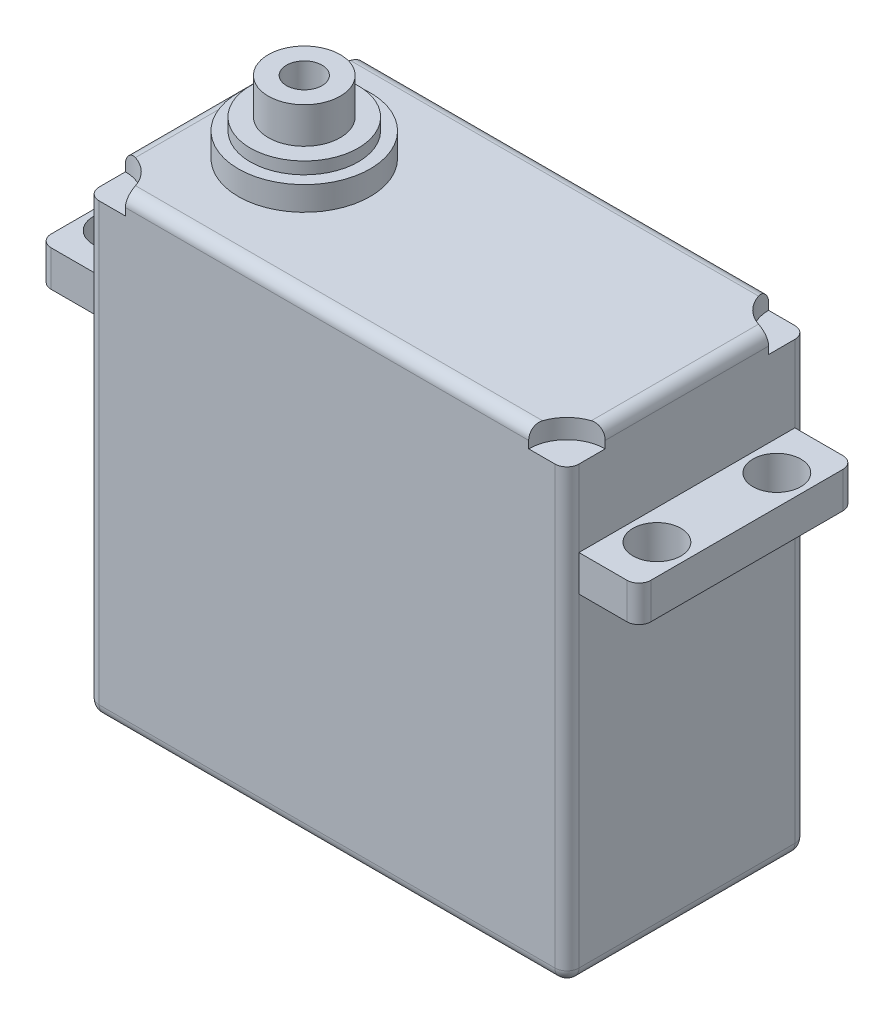
SolidWorks part; units mm, degrees
ref_plane "前视基准面" through (0, 0, 0) normal (0, 0, 1) x (1, 0, 0)
ref_plane "上视基准面" through (0, 0, 0) normal (0, 1, 0) x (1, 0, 0)
ref_plane "右视基准面" through (0, 0, 0) normal (1, 0, 0) x (0, 0, -1)
other "Configuration Table"
sketch "草图1" plane through (0, 0, 0) normal (0, 0, 1) x (1, 0, 0)
  line L0 (-19.2, 17.8947) -> (-19.2, -17.89)
  line L1 (-20, 19.5) -> (20, 19.5)
  line L2 (-20, 19.5) -> (-20, -19.5)
  line L3 (-20, -19.5) -> (20, -19.5)
  line L4 (20, 19.5) -> (20, -19.5)
  line L5 (-20, 19.5) -> (20, -19.5) construction
  line L6 (-20, -19.5) -> (20, 19.5) construction
  line L9 (-20, 17.8947) -> (-16.8102, 17.8947)
  line L10 (-16.8102, 19.5) -> (-16.8102, 17.8947)
  line L13 (-20, -17.89) -> (-16.81, -17.89)
  line L14 (-16.81, -19.5) -> (-16.81, -17.89)
  line L17 (20, 17.89) -> (16.81, 17.89)
  line L18 (16.81, 19.5) -> (16.81, 17.89)
  line L21 (20, -17.89) -> (16.81, -17.89)
  line L22 (16.81, -19.5) -> (16.81, -17.89)
  line L23 (-16.8102, 18.6974) -> (16.81, 18.695)
  line L24 (19.2, 17.89) -> (19.2, -17.89)
  line L25 (-16.81, -18.695) -> (16.81, -18.695)
  point P0 (0, 0)
  dimension "D1" = 40
  dimension "D2" = 39
  dimension "D3" = 1.6053
  dimension "D4" = 3.1898
  dimension "D5" = 1.61
  dimension "D6" = 3.19
  dimension "D7" = 1.61
  dimension "D8" = 3.19
  dimension "D9" = 3.19
  dimension "D10" = 1.61
  dimension "D11" = 0.8
  dimension "D12" = 0.8
extrude "凸台-拉伸1" add sketch "草图1" along normal blind 20 contours L4 L3 L2 L1
sketch "草图2" plane through (0, 19.5, 0) normal (0, 1, 0) x (1, 0, 0)
  line L1 (-20, 0) -> (-16.81, 0) construction
  line L2 (-20, -20) -> (-20, 0) construction
  line L3 (-20, -20) -> (20, -20) construction
  line L4 (-20, 0) -> (20, 0) construction
  line L5 (20, -20) -> (20, 0) construction
  line L6 (-19.2, 0) -> (-19.2, -20)
  line L7 (19.2, 0) -> (19.2, -20)
  line L8 (-20, -0.8) -> (20, -0.8)
  line L9 (-20, -19.2) -> (20, -19.2)
  circle A0 centre (-11.898, -10) radius 5.5
  circle A1 centre (-11.898, -10) radius 4.5
  circle A2 centre (-11.898, -10) radius 3
  circle A3 centre (-11.898, -10) radius 1.4031
  circle A4 centre (-20, 0) radius 3.1063
  circle A5 centre (-20, -20) radius 3.19
  circle A6 centre (20, 0) radius 3.19
  circle A7 centre (20, -20) radius 3.19
  line M2 (20, 0) -> (-20, 0)
  line M3 (-20, 0) -> (-20, -20)
  line M4 (-20, -20) -> (20, -20)
  line M5 (20, -20) -> (20, 0)
  dimension "D3" = 6
  dimension "D4" = 11
  dimension "D5" = 9
  dimension "D2" = 0.8
  dimension "D6" = 0.8
  dimension "D7" = 0.8
extrude "凸台-拉伸2" add sketch "草图2" along normal blind 6 contours A2
extrude "凸台-拉伸5" add sketch "草图2<5>" along normal blind 2 contours A0 A1 region at (-17.2425, 19.5, 10)
sketch "草图2<5>" plane through (0, 19.5, 0) normal (0, 1, 0) x (1, 0, 0) same geometry as "草图2"
extrude "凸台-拉伸6" add sketch "草图2<6>" along normal blind 3 contours A1 A2 region at (-16.2708, 19.5, 10)
sketch "草图2<6>" plane through (0, 19.5, 0) normal (0, 1, 0) x (1, 0, 0) same geometry as "草图2"
sketch "草图6" plane through (0, 25.5, 0) normal (0, 1, 0) x (1, 0, 0)
  circle A0 centre (-11.898, -10) radius 1.4811
sketch "草图7" plane through (20, 0, 0) normal (1, 0, 0) x (0, 0, -1)
  line L1 (-20, 19.5) -> (-20, -19.5) construction
  line L7 (-19, 11.5) -> (-19, 8.5)
  line L8 (-1, 11.5) -> (-1, 8.5)
  line L9 (0, 19.5) -> (0, -19.5) construction
  line L10 (-19, 11.5) -> (-1, 11.5)
  line L11 (-19, 8.5) -> (-1, 8.5)
  dimension "D3" = 1
  dimension "D4" = 1
sketch "草图12" plane through (-20, 0, 0) normal (-1, 0, 0) x (0, 0, 1)
  line L2 (20, 19.5) -> (20, -19.5) construction
  line L7 (19, 11.5) -> (19, 8.5)
  line L10 (1, 11.5) -> (1, 8.5)
  line L11 (0, 19.5) -> (0, -19.5) construction
  line L12 (1, 11.5) -> (19, 11.5)
  line L13 (1, 8.5) -> (19, 8.5)
  point P14 (19, 10)
  dimension "D3" = 1
  dimension "D4" = 1
extrude "切除-拉伸5" cut sketch "草图2<8>" against normal blind 1.61 contours L8 L6 M3 M2 | L8 A4 L6 M2 | L6 A4 L8 | A4 L6 L8 M3 region at (-18.064, 19.5, 0.3969) region at (-19.6, 19.5, 0.4) region at (-18.3367, 19.5, 1.6633) region at (-19.6031, 19.5, 1.936)
sketch "草图2<8>" plane through (0, 19.5, 0) normal (0, 1, 0) x (1, 0, 0) same geometry as "草图2"
extrude "切除-拉伸6" cut sketch "草图2<12>" against normal blind 1.61 contours L7 L8 M5 M2 | L7 A6 L8 M5 | L8 A6 L7 | A6 L8 L7 M2 | A7 L7 L9 M5 | L9 L7 M4 M5 | L9 A7 L7 M4 | L7 A7 L9 | A5 L9 L6 M4 | L9 A5 L6 | L6 A5 L9 M3 | L9 L6 M3 M4 region at (18.0217, 19.5, 0.3971) region at (-18.3008, 19.5, 18.3008) region at (-19.6029, 19.5, 18.0217) region at (18.3008, 19.5, 1.6992) region at (19.6, 19.5, 0.4) region at (-18.0217, 19.5, 19.6029) region at (-19.6, 19.5, 19.6) region at (19.6029, 19.5, 1.9783) region at (18.3008, 19.5, 18.3008) region at (18.0217, 19.5, 19.6029) region at (19.6029, 19.5, 18.0217) region at (19.6, 19.5, 19.6)
sketch "草图2<12>" plane through (0, 19.5, 0) normal (0, 1, 0) x (1, 0, 0) same geometry as "草图2"
fillet "圆角2" radius 1 1 edges at (-0.0419, 19.5, 0)
fillet "圆角3" radius 1 3 edges at (20, 19.5, 10) (0, 19.5, 20) (-20, 19.5, 9.9581)
fillet "圆角5" radius 1 1 edges at (-20, -0.805, 0)
fillet "圆角6" radius 1 3 edges at (20, -0.805, 0) (20, -0.805, 20) (-20, -0.805, 20)
fillet "圆角9" radius 1 8 edges at (-20, -19.5, 10) (0, -19.5, 0) (20, -19.5, 10) (0, -19.5, 20) (-19.7071, -19.5, 19.7071) (-19.7071, -19.5, 0.2929) (19.7071, -19.5, 0.2929) (19.7071, -19.5, 19.7071)
extrude "切除-拉伸11" cut sketch "草图6" against normal blind 3
extrude "凸台-拉伸10" add sketch "草图7" along normal blind 5
sketch "草图14" plane through (0, 11.5, 0) normal (0, 1, 0) x (1, 0, 0)
  circle A0 centre (22.5, -5) radius 2
  circle A1 centre (22.5, -15) radius 2
  dimension "D1" = 4
  dimension "D2" = 10
extrude "切除-拉伸12" cut sketch "草图14" against normal through all
extrude "凸台-拉伸11" add sketch "草图12" along normal blind 5
sketch "草图15" plane through (0, 11.5, 0) normal (0, 1, 0) x (1, 0, 0)
  circle A0 centre (-22.5, -5) radius 2
  circle A1 centre (-22.5, -15) radius 2
  dimension "D1" = 10
extrude "切除-拉伸13" cut sketch "草图15" against normal through all
fillet "圆角10" radius 1 4 edges at (-25, 10, 1) (-25, 10, 19) (25, 10, 19) (25, 10, 1)
